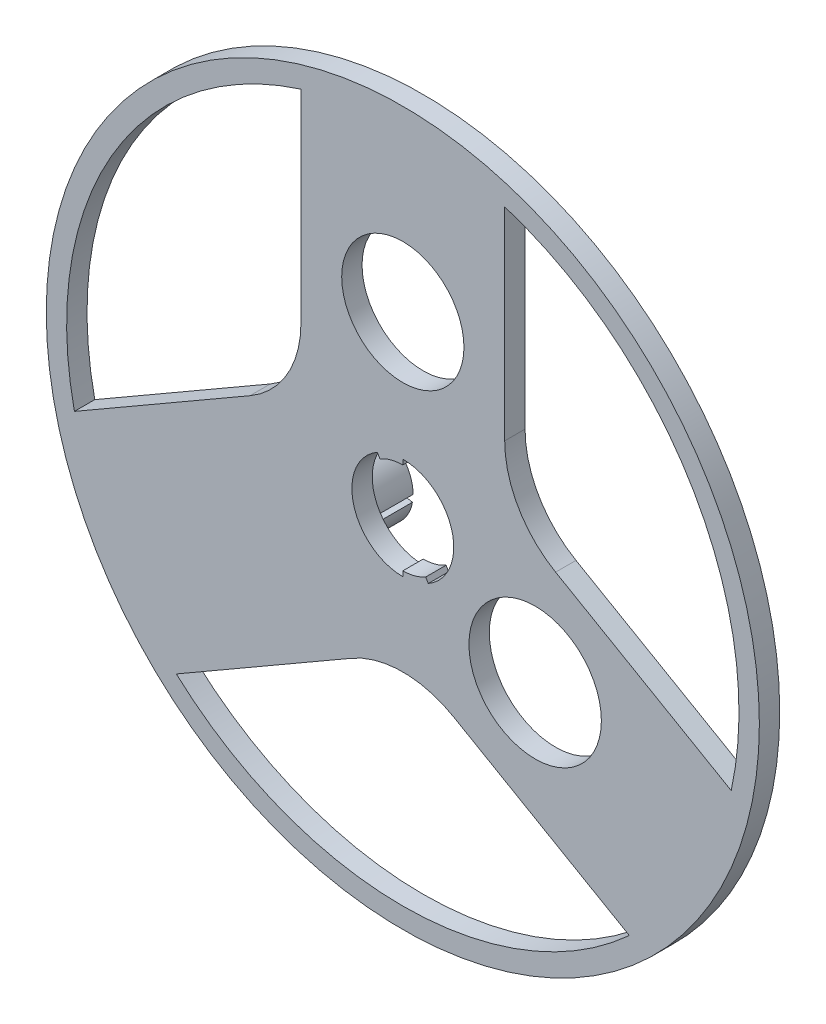
SolidWorks part; units mm, degrees
ref_plane "Front Plane" through (0, 0, 0) normal (0, 0, 1) x (1, 0, 0)
ref_plane "Top Plane" through (0, 0, 0) normal (0, 1, 0) x (1, 0, 0)
ref_plane "Right Plane" through (0, 0, 0) normal (1, 0, 0) x (0, 0, -1)
sketch "Sketch1" plane through (0, 0, 0) normal (0, 0, 1) x (1, 0, 0)
  line L0 (0, 0) -> (0, 33) construction
  line L1 (0, 0) -> (-10, 5.7735)
  line L2 (-10, 5.7735) -> (-10, 31.4484)
  line L3 (0, 0) -> (10, 5.7735)
  line L4 (10, 5.7735) -> (10, 31.4484)
  line L5 (10, 5.7735) -> (32.2351, -7.0639)
  line L6 (0, -11.547) -> (22.2351, -24.3844)
  line L7 (0, 0) -> (0, -11.547)
  line L8 (0, 0) -> (10, 5.7735)
  line L9 (0, -11.547) -> (-22.2351, -24.3844)
  line L10 (-10, 5.7735) -> (-32.2351, -7.0639)
  line L11 (0, 0) -> (-10, 5.7735)
  line L12 (0, 0) -> (0, -11.547)
  circle A0 centre (0, 0) radius 35
  circle A2 centre (0, 0) radius 33
  point P20 (0, 0)
  dimension "D1" = 70
  dimension "D2" = 10
  dimension "D3" = 66
  dimension "D4" = 60
  dimension "D5" = 3
extrude "Boss-Extrude1" add sketch "Sketch1" along normal blind 2 contours L1 L0 A2 L2 | L0 L3 L4 A2 | L6 A2 L5 L3 L7 | L10 A2 L9 L7 L1 | A0 A2 L9 region at (-4.794, 17.6439, 0) region at (-15.2801, -8.822, 0) region at (4.794, 17.6439, 0) region at (15.2801, -8.822, 0) region at (-34.0101, 0, 0)
fillet "Fillet1" radius 10 3 edges at (10, 5.7735, 1) (0, -11.547, 1) (-10, 5.7735, 1)
sketch "Sketch3" plane through (0, 0, 0) normal (0, 0, -1) x (-1, 0, 0)
  line L0 (0, 0) -> (0, 35) construction
  line L1 (0, 0) -> (30.3109, -17.5) construction
  line L2 (0, 0) -> (-30.3109, -17.5) construction
  line L3 (-5, -14.4338) -> (-22.2351, -24.3844) construction
  line L4 (5, -14.4338) -> (22.2351, -24.3844) construction
  line L5 (12.9904, -7.5) -> (12.9904, -3.5)
  line L6 (12.9904, -7.5) -> (16.9296, -6.8054)
  line L7 (12.9904, -7.5) -> (13.685, -11.4392)
  line L8 (12.9904, -7.5) -> (16.9904, -7.5)
  line L9 (12.9904, -7.5) -> (9.0512, -8.1946)
  line L10 (12.9904, -7.5) -> (12.9904, -11.5)
  line L11 (12.9904, -7.5) -> (12.2958, -3.5608)
  line L12 (12.9904, -7.5) -> (8.9904, -7.5)
  circle A0 centre (0, 0) radius 15 construction
  circle A1 centre (0, 0) radius 35 construction
  circle A2 centre (0, 17.5) radius 6
  circle A3 centre (-12.9904, -7.5) radius 6.5
  circle A4 centre (12.9904, -7.5) radius 3.3
  circle A5 centre (12.9904, -7.5) radius 4
  point P31 (12.9904, -7.5)
  dimension "D1" = 30
  dimension "D2" = 12
  dimension "D3" = 13
  dimension "D4" = 6.6
  dimension "D5" = 8
  dimension "D6" = 80
  dimension "D7" = 4
sketch "Sketch2" plane through (0, 0, 0) normal (0, 0, -1) x (-1, 0, 0)
  line L0 (0, 0) -> (0, 35) construction
  line L1 (0, 0) -> (0, 5) construction
  line L2 (0, 0) -> (2.5, 4.3301) construction
  line L3 (0, 5) -> (0, 4.5)
  line L4 (2.5, 4.3301) -> (2.25, 3.8971)
  line L5 (0, -5) -> (0, -4.5)
  line L6 (-2.5, -4.3301) -> (-2.25, -3.8971)
  circle A0 centre (0, 0) radius 5
  circle A1 centre (0, 0) radius 35 construction
  circle A2 centre (0, 0) radius 4.5
  point P19 (0, 0)
  dimension "D1" = 10
  dimension "D2" = 9
  dimension "D4" = 30
  dimension "D5" = 2
extrude "Cut-Extrude2" cut sketch "Sketch2" against normal up to next contours A2 | A2 L5 A0 L4 | A2 L3 A0 L6 region at (0.1059, 4.75, 0) region at (0, 0, 0) region at (-4.2385, 2.4471, 0)
extrude "Cut-Extrude3" cut sketch "Sketch3" against normal up to next contours A3 | A2 region at (0, 17.5, 0) region at (12.9904, -7.5, 0)
extrude "Boss-Extrude2" add sketch "Sketch3<4>" along normal blind 8 contours L7 A5 L8 A4 | L6 A5 L5 A4 | L11 A5 L12 A4 | L9 A5 L10 A4 region at (-15.1572, -4.9177, 0) region at (-15.5727, -9.6668, 0) region at (-10.8236, -10.0823, 0) region at (-10.4081, -5.3332, 0)
sketch "Sketch3<4>" plane through (0, 0, 0) normal (0, 0, -1) x (-1, 0, 0) same geometry as "Sketch3"
chamfer "Chamfer1" distance 1 angle 45 4 edges at (-15.5615, -4.4358, 0) (-9.9262, -4.9288, 0) (-10.4192, -10.5642, 0) (-16.0546, -10.0712, 0)
